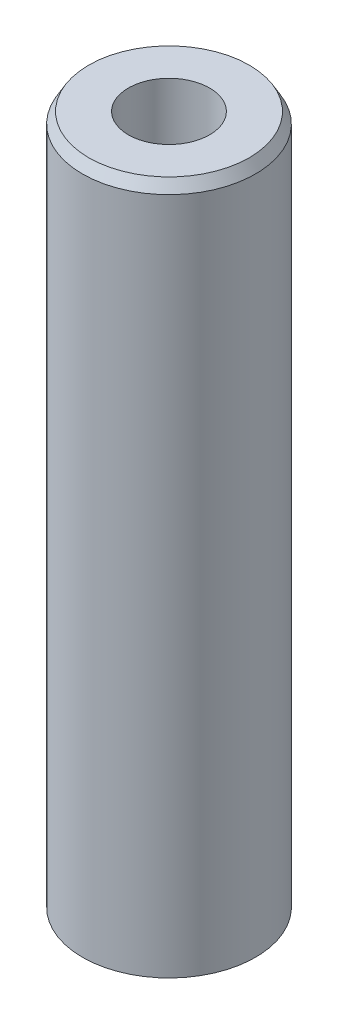
SolidWorks part; units mm, degrees
ref_plane "Front Plane" through (0, 0, 0) normal (0, 0, 1) x (1, 0, 0)
ref_plane "Top Plane" through (0, 0, 0) normal (0, 1, 0) x (1, 0, 0)
ref_plane "Right Plane" through (0, 0, 0) normal (1, 0, 0) x (0, 0, -1)
sketch "Sketch1" plane through (0, 0, 0) normal (0, 1, 0) x (1, 0, 0)
  circle A0 centre (0, 0) radius 12.5
  dimension "SHAFT_OD" = 25
extrude "Boss-Extrude1" add sketch "Sketch1" along normal blind 100.4526
sketch "Sketch2" plane through (0, 0, 0) normal (0, 1, 0) x (1, 0, 0)
  circle A0 centre (0, 0) radius 5.8647
  dimension "BORE_D" = 11.7294
extrude "Cut-Extrude1" cut sketch "Sketch2" along normal through all
chamfer "Chamfer1" distance 1.5756 angle 30 2 edges at (0, 100.4526, 12.5) (0, 0, 12.5) first distance on face at (0, 100.4526, 12.5) first distance on face at (0, 0, 5.8647)
